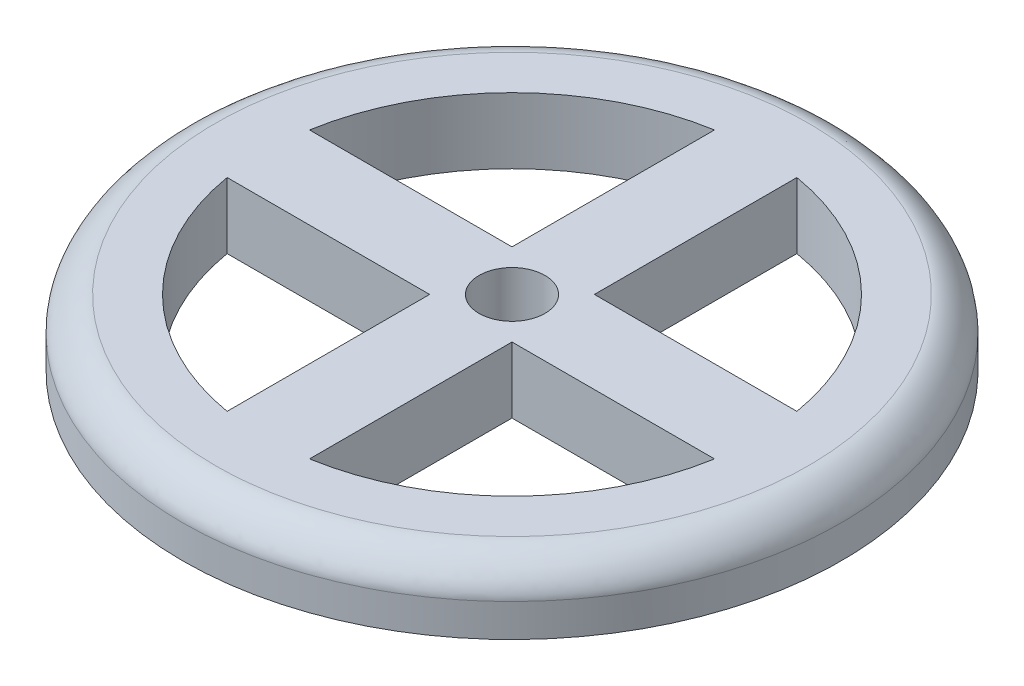
SolidWorks part; units mm, degrees
ref_plane "Front Plane" through (0, 0, 0) normal (0, 0, 1) x (1, 0, 0)
ref_plane "Top Plane" through (0, 0, 0) normal (0, 1, 0) x (1, 0, 0)
ref_plane "Right Plane" through (0, 0, 0) normal (1, 0, 0) x (0, 0, -1)
sketch "Sketch2" plane through (0, 0, 0) normal (0, 1, 0) x (1, 0, 0)
  line L14 (-2.5, 14.7902) -> (-2.5, -14.7902)
  line L16 (2.5, 14.7902) -> (2.5, -14.7902)
  line L17 (-2.5, 14.7902) -> (2.5, -14.7902) construction
  line L18 (-2.5, -14.7902) -> (2.5, 14.7902) construction
  line L19 (-14.7902, 2.5) -> (14.7902, 2.5)
  line L21 (-14.7902, -2.5) -> (14.7902, -2.5)
  line L23 (-14.7902, 2.5) -> (14.7902, -2.5) construction
  line L24 (-14.7902, -2.5) -> (14.7902, 2.5) construction
  circle A0 centre (0, 0) radius 20
  circle A2 centre (0, 0) radius 2
  circle A3 centre (0, 0) radius 15
  dimension "D1" = 40
  dimension "D2" = 30
  dimension "D4" = 5
extrude "Boss-Extrude1" add sketch "Sketch2" along normal blind 4 contours A0 | L21 A3 L19 L16 | L16 A3 L14 L19 | L19 A3 L21 L14 | L14 A3 L16 L21 | L14 L21 L16 L19 A2 region at (0, 0, -8.7153) region at (0, 0, -2.4293) region at (-8.7153, 0, 0) region at (0, 0, 8.7153) region at (8.7153, 0, 0) region at (-19.4343, 0, 0)
fillet "Fillet2" radius 2 1 edges at (0, 4, 20) conic radius 3
